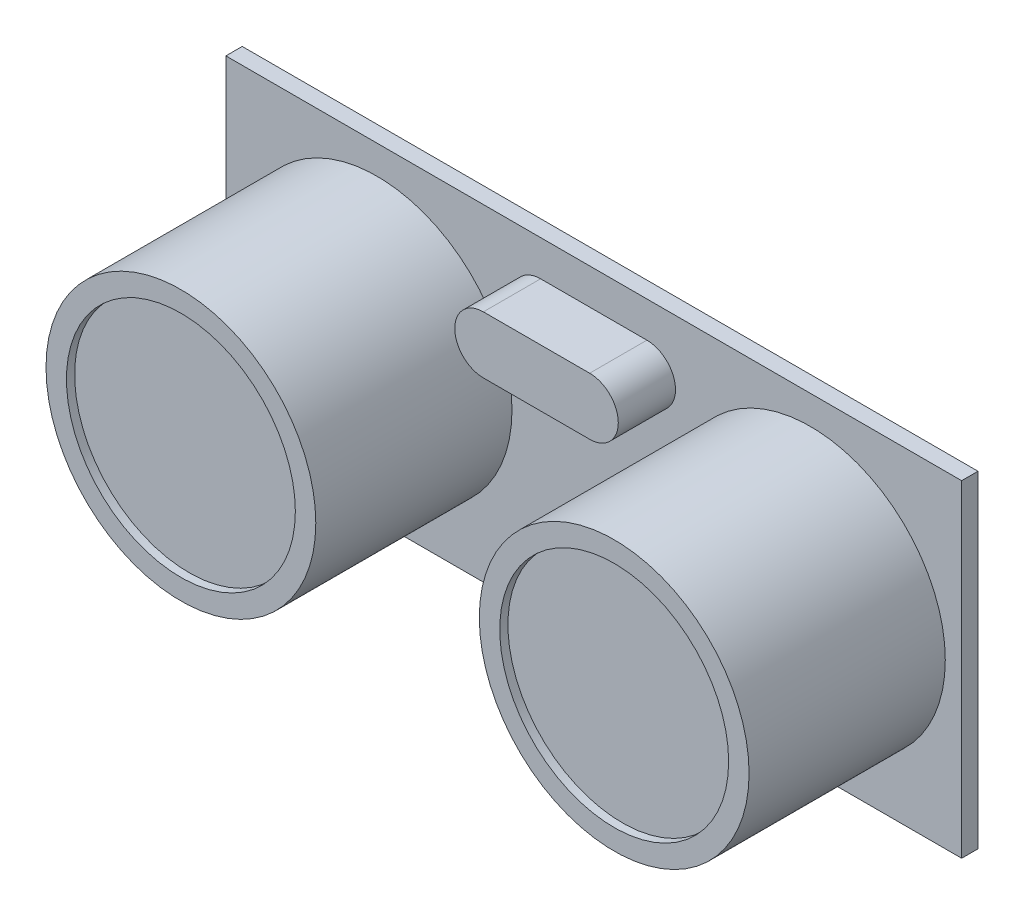
SolidWorks part; units mm, degrees
ref_plane "Plano frontal" through (0, 0, 0) normal (0, 0, 1) x (1, 0, 0)
ref_plane "Plano superior" through (0, 0, 0) normal (0, 1, 0) x (1, 0, 0)
ref_plane "Plano direito" through (0, 0, 0) normal (1, 0, 0) x (0, 0, -1)
sketch "Esboço1" plane through (0, 0, 0) normal (0, 0, 1) x (1, 0, 0)
  line L1 (0, 0) -> (45, 0)
  line L2 (0, 0) -> (0, 20)
  line L3 (0, 20) -> (45, 20)
  line L4 (45, 0) -> (45, 20)
  dimension "D1" = 45
  dimension "D2" = 20
extrude "Ressalto-extrusão1" add sketch "Esboço1" along normal blind 1
sketch "Esboço2" plane through (0, 0, 1) normal (0, 0, 1) x (1, 0, 0)
  line L0 (0, 10) -> (45, 10) construction
  line L1 (0, 20) -> (0, 0) construction
  line L2 (45, 0) -> (45, 20) construction
  line L3 (9.25, 20) -> (9.25, 0) construction
  line L4 (45, 20) -> (0, 20) construction
  line L5 (0, 0) -> (45, 0) construction
  line L6 (35.75, 20) -> (35.75, 0) construction
  circle A0 centre (9.25, 10) radius 8.25
  circle A1 centre (35.75, 10) radius 8.25
  dimension "D1" = 26.5
  dimension "D3" = 16.5
  dimension "D4" = 16.5
  dimension "D2" = 9.25
extrude "Ressalto-extrusão2" add sketch "Esboço2" along normal blind 12
sketch "Esboço3" plane through (0, 0, 13) normal (0, 0, 1) x (1, 0, 0)
  circle A0 centre (9.25, 10) radius 7
  circle A1 centre (35.75, 10) radius 7
extrude "Corte-extrusão1" cut sketch "Esboço3" against normal blind 0.5
sketch "Esboço6" plane through (0, 0, 1) normal (0, 0, 1) x (1, 0, 0)
  line L0 (22.5, 20) -> (22.5, 0) construction
  line L1 (17.5, 14.3168) -> (27.5, 14.3168)
  line L2 (17.5, 14.3168) -> (17.5, 17.8168)
  line L3 (17.5, 17.8168) -> (27.5, 17.8168)
  line L4 (27.5, 14.3168) -> (27.5, 17.8168)
  line L5 (45, 20) -> (0, 20) construction
  line L6 (0, 0) -> (45, 0) construction
  circle A2 centre (19.25, 16.0668) radius 1.75
  circle A3 centre (25.75, 16.0668) radius 1.75
  dimension "D1" = 10
  dimension "D2" = 3.5
  dimension "D3" = 5
extrude "Ressalto-extrusão5" add sketch "Esboço6" along normal blind 3.5 contours A2 | L0 L3 A2 L1 | L3 L0 L1 A3 | A3 region at (23.4784, 16.0668, 1) region at (21.5216, 16.0668, 1) region at (19.25, 16.0668, 1) region at (25.75, 16.0668, 1)
sketch "Esboço7" plane through (0, 0, 0) normal (0, 0, -1) x (-1, 0, 0)
  line L0 (0, 0) -> (-45, 0) construction
  line L1 (-27.5, 0) -> (-17.5, 0)
  line L2 (-27.5, 0) -> (-27.5, 2)
  line L3 (-27.5, 2) -> (-17.5, 2)
  line L4 (-17.5, 0) -> (-17.5, 2)
  line L5 (-22.5, 20) -> (-22.5, 0) construction
  line L6 (-25.5, 2) -> (-25.5, 0)
  line L7 (-45, 20) -> (0, 20) construction
  line L8 (-23.5, 2) -> (-23.5, 0)
  line L9 (-21.5, 2) -> (-21.5, 0)
  line L10 (-19.5, 2) -> (-19.5, 0)
  line L11 (-25.6, 2) -> (-25.6, 0)
  line L12 (-23.6, 2) -> (-23.6, 0)
  line L13 (-21.6, 2) -> (-21.6, 0)
  line L14 (-19.6, 2) -> (-19.6, 0)
  line L15 (-27.6, -0.1) -> (-27.6, 2.1)
  line L16 (-27.6, 2.1) -> (-17.4, 2.1)
  line L17 (-17.4, -0.1) -> (-17.4, 2.1)
  line L18 (-27.6, -0.1) -> (-17.4, -0.1)
  line L19 (-25.4, 2) -> (-25.4, 0)
  line L20 (-23.4, 2) -> (-23.4, 0)
  line L21 (-21.4, 2) -> (-21.4, 0)
  line L22 (-19.4, 2) -> (-19.4, 0)
  line L23 (-27.4, 0.1) -> (-27.4, 1.9)
  line L24 (-27.4, 1.9) -> (-17.6, 1.9)
  line L25 (-17.6, 0.1) -> (-17.6, 1.9)
  line L26 (-27.4, 0.1) -> (-17.6, 0.1)
  line L28 (-25.6, 1.9) -> (-19.4, 1.9)
  line L29 (-25.6, 1.9) -> (-25.6, 0.1)
  line L30 (-25.6, 0.1) -> (-19.4, 0.1)
  line L31 (-19.4, 1.9) -> (-19.4, 0.1)
  line M23 (-45, 0) -> (0, 0)
  dimension "D1" = 5
  dimension "D2" = 10
  dimension "D3" = 2
  dimension "D4" = 2
  dimension "D5" = 2
  dimension "D6" = 2
  dimension "D7" = 2
  dimension "D10" = 0.1
  dimension "D11" = 0.1
  dimension "D8" = 0.1
  dimension "D9" = 0.1
extrude "Ressalto-extrusão6" add sketch "Esboço7" along normal blind 2 contours L23 L26 L11 L24 | L19 L26 L12 L24 | L5 L24 L20 L26 | L28 L5 L30 L13 | L21 L26 L14 L24 | L22 L26 L25 L24 | L26 L23 L24 L11 L3 L2 M23 | L19 L24 L12 L3 | L5 L3 L20 L24 | L3 L5 L28 L13 | L21 L24 L14 L3 | L26 L22 L1 L4 L3 L24 L25 | L26 L19 L12 M23 | L5 L26 L20 L1 | L30 L5 L13 M23 | L26 L21 L14 M23 region at (27.4724, 1, 0) region at (26.5, 1, 0) region at (24.5, 0.05, 0) region at (24.5, 1, 0) region at (24.5, 1.95, 0) region at (22.95, 1.95, 0) region at (22.05, 1.95, 0) region at (18.45, 0.0276, 0) region at (22.05, 1, 0) region at (22.95, 1, 0) region at (22.95, 0.05, 0) region at (22.05, 0.05, 0) region at (18.5, 1, 0) region at (20.5, 1.95, 0) region at (20.5, 0.05, 0) region at (20.5, 1, 0)
sketch "Esboço9" plane through (0, 0, -2) normal (0, 0, -1) x (-1, 0, 0)
  line L0 (-17.5, 0) -> (-17.5, 2) construction
  line L1 (-27.5, 0) -> (-17.5, 0)
  line L2 (-27.5, 0) -> (-27.5, 0.1)
  line L3 (-27.5, 0.1) -> (-17.5, 0.1)
  line L4 (-17.5, 0) -> (-17.5, 0.1)
  dimension "D1" = 0.1
extrude "Corte-extrusão2" cut sketch "Esboço9" against normal blind 2
sketch "Esboço10" plane through (0, 0, -2) normal (0, 0, -1) x (-1, 0, 0)
  line L0 (-27.5, 1.05) -> (-25, 1.05) construction
  line L1 (-27.5, 0.1) -> (-27.5, 2) construction
  line L2 (-17.5, 0.1) -> (-17.5, 2) construction
  line L3 (-26.55, 2) -> (-26.55, 0.1) construction
  line L4 (-27.5, 2) -> (-25.6, 2) construction
  line L5 (-25.6, 0.1) -> (-27.5, 0.1) construction
  line L6 (-24.5, 2) -> (-24.5, 1.55) construction
  line L7 (-25.4, 2) -> (-23.6, 2) construction
  line L8 (-23.6, 0.1) -> (-25.4, 0.1) construction
  line L9 (-22.5, 2) -> (-22.5, 0.1) construction
  line L10 (-23.4, 2) -> (-21.6, 2) construction
  line L11 (-21.6, 0.1) -> (-23.4, 0.1) construction
  line L12 (-20.5, 2) -> (-20.5, 0.1) construction
  line L13 (-21.4, 2) -> (-19.6, 2) construction
  line L14 (-19.6, 0.1) -> (-21.4, 0.1) construction
  line L15 (-18.45, 2) -> (-18.45, 0.1) construction
  line L16 (-19.4, 2) -> (-17.5, 2) construction
  line L17 (-17.5, 0.1) -> (-19.4, 0.1) construction
  line L18 (-25, 0.55) -> (-24, 0.55)
  line L21 (-25, 1.55) -> (-24, 1.55)
  line L22 (-24, 0.55) -> (-24, 1.55)
  line L23 (-25, 0.55) -> (-25, 1.55)
  line L24 (-24.5, 0.55) -> (-24.5, 0.1) construction
  line L25 (-24, 1.05) -> (-17.5, 1.05) construction
  line L26 (-27.05, 0.55) -> (-26.05, 0.55)
  line L27 (-27.05, 1.55) -> (-26.05, 1.55)
  line L28 (-26.05, 0.55) -> (-26.05, 1.55)
  line L29 (-27.05, 0.55) -> (-27.05, 1.55)
  line L30 (-22.9724, 0.55) -> (-21.9724, 0.55)
  line L31 (-22.9724, 1.55) -> (-21.9724, 1.55)
  line L32 (-21.9724, 0.55) -> (-21.9724, 1.55)
  line L33 (-22.9724, 0.55) -> (-22.9724, 1.55)
  line L34 (-20.9694, 0.55) -> (-19.9694, 0.55)
  line L35 (-20.9694, 1.55) -> (-19.9694, 1.55)
  line L36 (-19.9694, 0.55) -> (-19.9694, 1.55)
  line L37 (-20.9694, 0.55) -> (-20.9694, 1.55)
  line L38 (-18.9714, 0.55) -> (-17.9714, 0.55)
  line L39 (-18.9714, 1.55) -> (-17.9714, 1.55)
  line L40 (-17.9714, 0.55) -> (-17.9714, 1.55)
  line L41 (-18.9714, 0.55) -> (-18.9714, 1.55)
  dimension "D1" = 0.5
  dimension "D2" = 0.5
  dimension "D3" = 0.5
  dimension "D4" = 1
  dimension "D5" = 1
  dimension "D6" = 1
  dimension "D7" = 1
  dimension "D8" = 1
  dimension "D9" = 1
  dimension "D10" = 1
  dimension "D11" = 1
  dimension "D12" = 1
  dimension "D13" = 1
  dimension "D14" = 0.5
  dimension "D15" = 0.5
  dimension "D16" = 0.5
  dimension "D17" = 0.5
  dimension "D18" = 0.5
extrude "Ressalto-extrusão7" add sketch "Esboço10" along normal blind 2
sketch "Esboço11" plane through (0, 0.55, 0) normal (0, -1, 0) x (1, 0, 0)
  line L0 (26.05, -4) -> (26.05, -2) construction
  line L1 (27.05, -4) -> (26.05, -4)
  line L2 (27.05, -4) -> (27.05, -3)
  line L3 (27.05, -3) -> (26.05, -3)
  line L4 (26.05, -4) -> (26.05, -3)
  line L21 (24, -4) -> (24, -2) construction
  line L22 (25, -4) -> (24, -4)
  line L23 (25, -4) -> (25, -3)
  line L24 (25, -3) -> (24, -3)
  line L25 (24, -4) -> (24, -3)
  line L26 (22.9724, -4) -> (22.9724, -2) construction
  line L27 (22.9724, -4) -> (21.9724, -4)
  line L28 (22.9724, -4) -> (22.9724, -3.0323)
  line L29 (22.9724, -3.0323) -> (21.9724, -3.0323)
  line L30 (21.9724, -4) -> (21.9724, -3.0323)
  line L31 (21.9724, -4) -> (21.9724, -2) construction
  line L32 (19.9694, -4) -> (19.9694, -2) construction
  line L33 (20.9694, -4) -> (19.9694, -4)
  line L34 (20.9694, -4) -> (20.9694, -3.0323)
  line L35 (20.9694, -3.0323) -> (19.9694, -3.0323)
  line L36 (19.9694, -4) -> (19.9694, -3.0323)
  line L37 (17.9714, -4) -> (17.9714, -2) construction
  line L38 (18.9714, -4) -> (17.9714, -4)
  line L39 (18.9714, -4) -> (18.9714, -3.0323)
  line L40 (18.9714, -3.0323) -> (17.9714, -3.0323)
  line L41 (17.9714, -4) -> (17.9714, -3.0323)
  dimension "D1" = 1
extrude "Ressalto-extrusão8" add sketch "Esboço11" along normal blind 4
